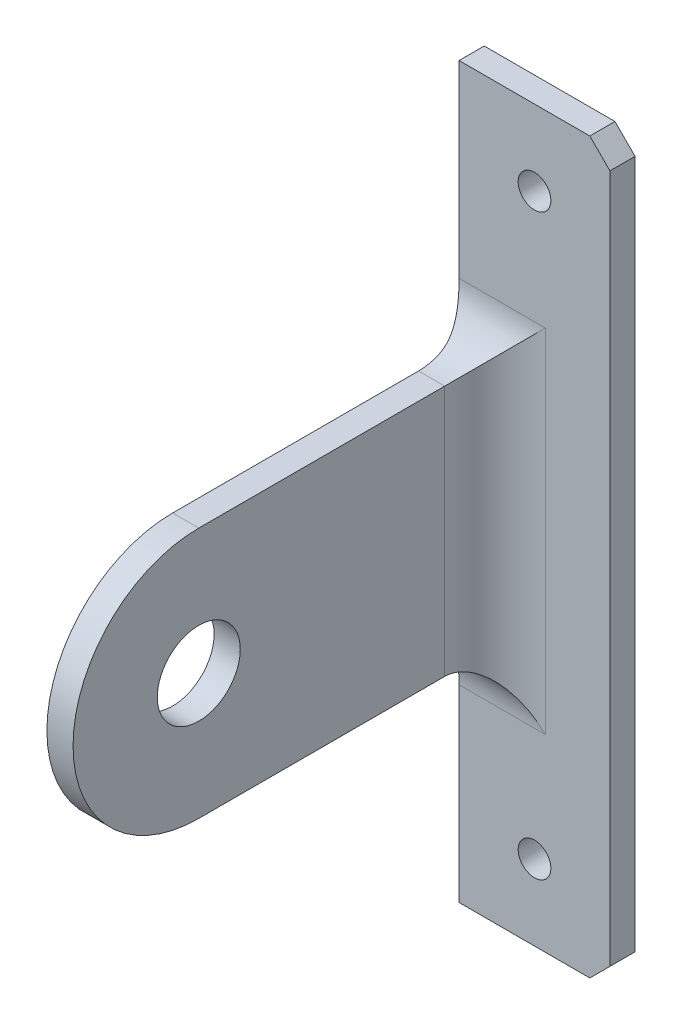
SolidWorks part; units mm, degrees
ref_plane "Front Plane" through (0, 0, 0) normal (0, 0, 1) x (1, 0, 0)
ref_plane "Top Plane" through (0, 0, 0) normal (0, 1, 0) x (1, 0, 0)
ref_plane "Right Plane" through (0, 0, 0) normal (1, 0, 0) x (0, 0, -1)
sketch "Sketch1" plane through (0, 0, 0) normal (1, 0, 0) x (0, 0, -1)
  line L1 (0, 12.5) -> (34.45, 12.5)
  line L2 (0, 4.125) -> (0, -12.5)
  line L3 (0, -12.5) -> (34.45, -12.5)
  line L4 (34.45, 12.5) -> (34.45, -12.5)
  circle A0 centre (0, 0) radius 4.125
  circle A1 centre (0, 0) radius 12.5 construction
  arc A2 (0, 12.5) -> (0, -12.5) centre (0, 0) ccw
  dimension "D1" = 8.25
  dimension "D2" = 25
  dimension "D3" = 34.45
extrude "Boss-Extrude1" add sketch "Sketch1" along normal blind 2.6 contours L1 A2 A0 L3 L4 region at (0, 0, -12.849)
sketch "Sketch2" [suppressed] plane through (0, 0, 0) normal (-1, 0, 0) x (0, 0, 1)
  circle A0 centre (0, 0) radius 1.5
  circle A1 centre (0, 0) radius 4.5
  dimension "D1" = 9
  dimension "D2" = 3
sketch "Sketch4" [suppressed] plane through (2.5, 0, 0) normal (1, 0, 0) x (0, 0, -1)
  circle A0 centre (0, 0) radius 2.5
sketch "Sketch5" [suppressed] plane through (2.5, 0, 0) normal (1, 0, 0) x (0, 0, -1)
  circle A0 centre (0, 0) radius 4.5
  circle A1 centre (0, 0) radius 2.5
  dimension "D1" = 9
  dimension "D2" = 5
sketch "Sketch6" plane through (0, 0, -34.45) normal (0, 0, -1) x (-1, 0, 0)
  line L1 (-8.8125, 36.25) -> (53.3216, 36.25)
  line L3 (6.25, -36.25) -> (53.3216, -36.25)
  line L4 (53.3216, 36.25) -> (53.3216, -36.25)
  line L6 (53.3216, -36.25) -> (-19.1784, 36.25) construction
  line L7 (6.25, -36.25) -> (-19.1784, -36.25)
  line L9 (-8.8125, 36.25) -> (-19.1784, 36.25)
  line L10 (-19.1784, -36.25) -> (-19.1784, 36.25)
  line L11 (53.3216, 36.25) -> (-19.1784, -36.25) construction
  point P4 (17.0716, 0)
  dimension "D1" = 72.5
  dimension "D2" = 72.5
extrude "Boss-Extrude4" add sketch "Sketch6" against normal blind 2.5
ref_plane "Plane1" through (-17.0716, 0, 0) normal (1, 0, 0) x (0, 0, -1)
ref_plane "Plane2" through (9.4784, 0, 0) normal (1, 0, 0) x (0, 0, -1)
sketch "Sketch7" plane through (0, 0, -31.95) normal (0, 0, 1) x (1, 0, 0)
  line L7 (1.7881, -3.3824) -> (-5.2119, -3.3824)
  line L12 (1.7881, -3.3824) -> (1.7881, -19.8824)
  line L18 (1.7881, -19.8824) -> (-5.2119, -19.8824)
  line L19 (-5.2119, -3.3824) -> (-5.2119, -19.8824)
  line L20 (1.7881, -3.3824) -> (-5.2119, -19.8824) construction
  line L21 (1.7881, -19.8824) -> (-5.2119, -3.3824) construction
  line L22 (-24.5, -4) -> (-8.5, -4)
  line L23 (-24.5, -4) -> (-24.5, 4)
  line L24 (-24.5, 4) -> (-8.5, 4)
  line L25 (-8.5, -4) -> (-8.5, 4)
  line L26 (-24.5, -4) -> (-8.5, 4) construction
  line L27 (-24.5, 4) -> (-8.5, -4) construction
  point P0 (-16.5, 0)
  point P2 (-1.7119, -11.6324)
  dimension "D1" = 16
  dimension "D2" = 16.5
  dimension "D3" = 7
  dimension "D4" = 8
extrude "Cut-Extrude2" cut sketch "Sketch7" against normal up to next
sketch "Sketch8" plane through (0, 0, 0) normal (0, 1, 0) x (1, 0, 0)
  line L10 (2.6, 4.125) -> (0, 4.125)
  line L15 (2.6, 4.125) -> (2.6, 31.95)
  line L16 (2.6, 31.95) -> (0, 31.95)
  line L21 (0, 4.125) -> (0, 31.95)
sketch "Sketch9" plane through (0, -12.5, 0) normal (0, -1, 0) x (1, 0, 0)
  line L0 (2.6, 0) -> (2.6, -31.95) construction
  line L1 (0, -31.95) -> (2.6, -31.95)
  line L2 (0, -31.95) -> (0, -9.5612)
  line L3 (0, -9.5612) -> (2.6, -9.5612)
  line L4 (2.6, -31.95) -> (2.6, -9.5612)
extrude "Cut-Extrude3" cut sketch "Sketch9" against normal up to next
extrude "Boss-Extrude5" add sketch "Sketch8" along normal mid plane 25
fillet "Fillet1" [suppressed] radius 4
fillet "Fillet2" radius 1 8 edges at (-5.2119, -3.3824, -33.2) (-5.2119, -19.8824, -33.2) (1.7881, -3.3824, -33.2) (-8.5, 4, -33.2) (1.7881, -19.8824, -33.2) (-8.5, -4, -33.2) (-24.5, 4, -33.2) (-24.5, -4, -33.2)
fillet "Fillet3" radius 4 4 edges at (19.1784, -36.25, -33.2) (19.1784, 36.25, -33.2) (-53.3216, 36.25, -33.2) (-53.3216, -36.25, -33.2)
sketch "Sketch10" plane through (0, 0, 0) normal (0, 1, 0) x (1, 0, 0)
  line L0 (15.1784, 31.95) -> (19.1784, 31.95) construction
  line L1 (21.7259, 31.95) -> (-56.5098, 31.95)
  line L2 (21.7259, 31.95) -> (21.7259, 38.24)
  line L3 (21.7259, 38.24) -> (-56.5098, 38.24)
  line L4 (-56.5098, 31.95) -> (-56.5098, 38.24)
extrude "Cut-Extrude4" cut sketch "Sketch10" against normal through all both and the other way through all
sketch "Sketch11" plane through (0, 0, 0) normal (0, 1, 0) x (1, 0, 0)
  line L1 (14.03, 31.95) -> (-0.97, 31.95)
  line L2 (14.03, 31.95) -> (14.03, 29.45)
  line L3 (14.03, 29.45) -> (-0.97, 29.45)
  line L4 (-0.97, 31.95) -> (-0.97, 29.45)
  line L6 (2.6, 31.95) -> (0, 31.95) construction
  line L7 (0, 31.95) -> (0, 0) construction
  dimension "D1" = 2.5
  dimension "D2" = 15
  dimension "D3" = 0.97
extrude "Boss-Extrude6" add sketch "Sketch11" along normal mid plane 25
sketch "Sketch12" plane through (0, 0, -31.95) normal (0, 0, -1) x (-1, 0, 0)
  line L0 (55, 0) -> (-55, 0) construction
  line L1 (-14.03, 36.25) -> (58.47, 36.25) construction
  line L2 (-14.03, 36.25) -> (-14.03, -36.25) construction
  line L3 (-14.03, -36.25) -> (58.47, -36.25) construction
  line L4 (58.47, 36.25) -> (58.47, -36.25) construction
  line L5 (-14.03, 36.25) -> (58.47, -36.25) construction
  line L6 (58.47, 36.25) -> (-14.03, -36.25) construction
  line L7 (-14.03, 12.5) -> (-14.03, -12.5) construction
  circle A0 centre (-6.53, 28.75) radius 1.5
  circle A1 centre (-6.53, -28.75) radius 1.5
  circle A2 centre (-6.53, 28.75) radius 3
  circle A3 centre (-6.53, -28.75) radius 3
  point P4 (-14.03, 0)
  dimension "D3" = 3
  dimension "D5" = 6
  dimension "D1" = 72.5
  dimension "D2" = 72.5
  dimension "D4" = 7.5
sketch "Sketch13" plane through (0, 0, -31.95) normal (0, 0, -1) x (-1, 0, 0)
  line L0 (-14.03, 12.5) -> (0.97, 12.5) construction
  line L1 (-14.03, 12.5) -> (0.97, 12.5)
  line L2 (-14.03, 12.5) -> (-14.03, 32.25)
  line L4 (0.97, 12.5) -> (0.97, 36.25)
  line L5 (0.97, 36.25) -> (-10.03, 36.25)
  line L6 (-14.03, 32.25) -> (-14.03, 36.25)
  line L7 (-14.03, 36.25) -> (-10.03, 36.25)
  dimension "D1" = 4
  dimension "D3" = 15
  dimension "D4" = 36.25
  dimension "D5" = 4
extrude "Boss-Extrude7" add sketch "Sketch13" against normal blind 2.5
mirror "Mirror1" about plane through (0, 0, 0) normal (0, 1, 0) of "Boss-Extrude6", "Boss-Extrude7"
sketch "Sketch14" plane through (0, 0, -31.95) normal (0, 0, -1) x (-1, 0, 0)
  line L1 (0.97, -36.25) -> (0.97, 36.25) construction
  line L2 (0.97, 36.25) -> (-14.03, 36.25) construction
  circle A0 centre (-6.53, 28.75) radius 1.625
  dimension "D3" = 3.25
  dimension "D1" = 7.5
  dimension "D2" = 7.5
extrude "Cut-Extrude5" cut sketch "Sketch14" against normal blind 2.5
sketch "Sketch15" [suppressed] plane through (0, 0, -31.95) normal (0, 0, -1) x (-1, 0, 0)
  circle A0 centre (-6.4288, 28.75) radius 2.5
  circle A1 centre (-6.4288, 28.75) radius 4
  dimension "D1" = 8
  dimension "D2" = 5
extrude "Boss-Extrude8" [suppressed] add sketch "Sketch15" against normal blind 6
mirror "Mirror2" about plane through (0, 0, 0) normal (0, 1, 0) of "Cut-Extrude5", "Boss-Extrude8"
fillet "Fillet4" radius 5 4 edges at (1.3, -12.5, -29.45) (0, 0, -29.45) (1.3, 12.5, -29.45) (2.6, 0, -29.45)
chamfer "Chamfer1" distance 2 angle 45 2 edges at (14.03, -36.25, -30.7) (14.03, 36.25, -30.7)
sketch "Sketch16" plane through (2.6, 0, 0) normal (1, 0, 0) x (0, 0, -1)
  line L0 (0, 12.5) -> (0, 10.5)
  line L1 (0, -10.5) -> (0, -12.5)
  arc A0 (0, 12.5) -> (0, -12.5) centre (0, 0) ccw
  arc A1 (0, 10.5) -> (0, -10.5) centre (0, 0) ccw
  dimension "D1" = 2
extrude "Boss-Extrude9" [suppressed] add sketch "Sketch16" along normal blind 9.5
